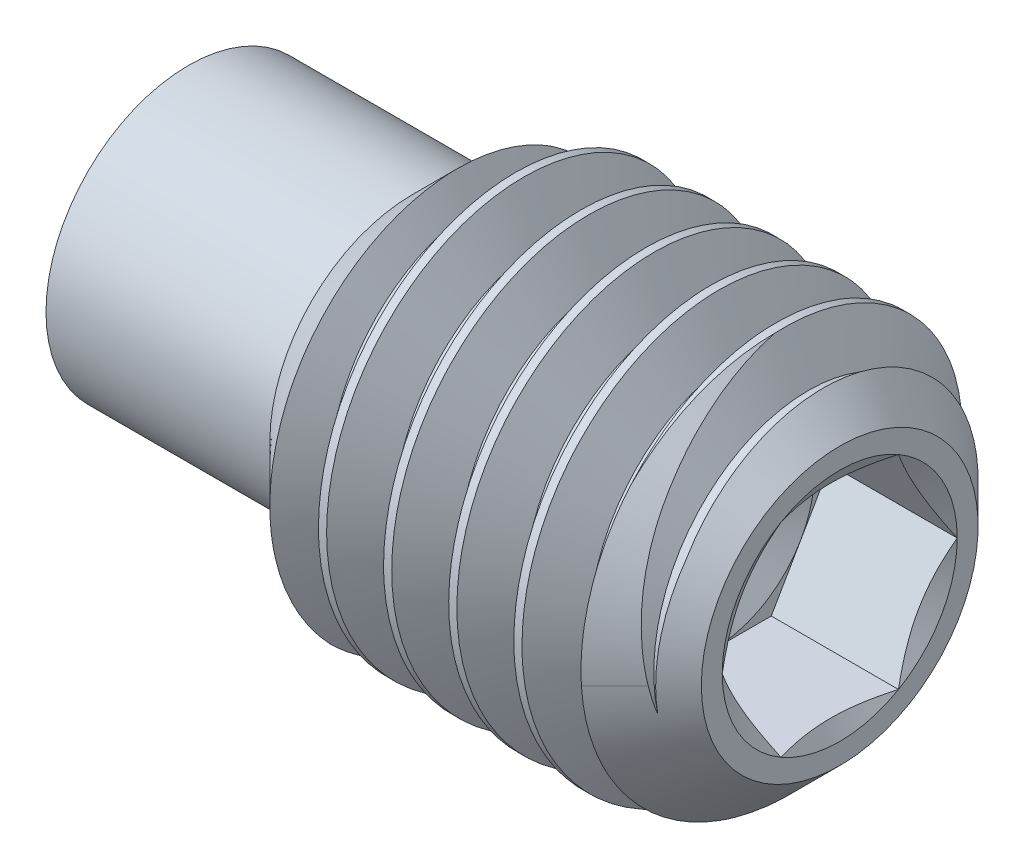
SolidWorks part; units mm, degrees
ref_plane "Front Plane" through (0, 0, 0) normal (0, 0, 1) x (1, 0, 0)
ref_plane "Top Plane" through (0, 0, 0) normal (0, 1, 0) x (1, 0, 0)
ref_plane "Right Plane" through (0, 0, 0) normal (1, 0, 0) x (0, 0, -1)
sketch "Sketch1" plane through (0, 0, 0) normal (0, 0, 1) x (1, 0, 0)
  line L0 (-4, 0) -> (4, 0) construction
  line L1 (4, 2.5) -> (4, -2.5) construction
  line L2 (-4, 1.75) -> (-4, -1.75) construction
  line L3 (4, 2.5) -> (3.2, 2.5) construction
  line L4 (-4, 1.75) -> (-1.25, 1.75) construction
  point P7 (2, -2.5)
  point P10 (4, 1.25)
  dimension "Length | l" = 8
  dimension "Tip Length | z" = 2.75
  dimension "Tip Diameter | dp" = 3.5
  dimension "Thread Diameter | d" = 5
  dimension "Thread Pitch | P1" = 0.8
  dimension "Drive Size | s" = 2.5
  dimension "D1" = 2
sketch "Sketch2" plane through (0, 0, 0) normal (0, 0, 1) x (1, 0, 0)
  line L0 (-4, 0) -> (-4, 1.75)
  line L1 (-4, 1.75) -> (-4, -1.75) construction
  line L2 (-4, 1.75) -> (-1.25, 1.75)
  line L3 (-1.25, 1.75) -> (-0.5, 2.5)
  line L4 (-0.5, 2.5) -> (3.2, 2.5)
  line L5 (4, 2.5) -> (3.2, 2.5) construction
  line L6 (3.2, 2.5) -> (4, 1.7)
  line L7 (4, 2.5) -> (4, -2.5) construction
  line L8 (4, 1.7) -> (4, 0)
  line L9 (4, 0) -> (-4, 0)
  dimension "D1" = 45
  dimension "D2" = 0.8
revolve "Revolve1" add sketch "Sketch2" angle 360 about L0
sketch "Sketch3" plane through (4, 0, 0) normal (1, 0, 0) x (0, 0, -1)
  line L0 (0, 1.75) -> (0, -1.75) construction
  line L1 (0.7217, 1.25) -> (-0.7217, 1.25)
  line L2 (-0.7217, 1.25) -> (-1.4434, 0)
  line L3 (-1.4434, 0) -> (-0.7217, -1.25)
  line L4 (-0.7217, -1.25) -> (0.7217, -1.25)
  line L5 (0.7217, -1.25) -> (1.4434, 0)
  line L6 (1.4434, 0) -> (0.7217, 1.25)
  circle A0 centre (0, 0) radius 1.25 construction
extrude "Cut-Extrude1" cut sketch "Sketch3" against normal blind 1.5625
sketch "Sketch4" plane through (4, 0, 0) normal (1, 0, 0) x (0, 0, -1)
  circle A0 centre (0, 0) radius 1.4434
extrude "Cut-Extrude2" cut sketch "Sketch4" against normal through all draft 60
sketch "Sketch5" plane through (2.4375, 0, 0) normal (1, 0, 0) x (0, 0, -1)
  circle A0 centre (0, 0) radius 1.25
  circle A1 centre (0, 0) radius 1.25 construction
extrude "Cut-Extrude3" cut sketch "Sketch5" against normal through all draft 60
ref_axis "Center Axis 1" through (-4, 0, 0) along (1, 0, 0)
sketch "Sketch6" plane through (0, 0, 0) normal (0, 0, 1) x (1, 0, 0)
  line L0 (4, 2.5) -> (4.35, 1.8938) construction
  line L1 (4.35, 1.8938) -> (4.7, 2.5) construction
  line L2 (4.7, 2.5) -> (4, 2.5) construction
  line L3 (4, 2.5) -> (3.95, 2.5866) construction
  line L4 (3.95, 2.5866) -> (4.75, 2.5866) construction
  line L5 (4.75, 2.5866) -> (4.7, 2.5) construction
  line L6 (4.3, 1.9804) -> (4.4, 1.9804) construction
  line L7 (4.35, 2.5866) -> (4.35, 2.5) construction
  line L8 (4.35, 1.9804) -> (4.35, 1.8938) construction
  line L9 (4, 2.5) -> (3.2, 2.5) construction
  line L10 (3.975, 2.5433) -> (4.725, 2.5433)
  line L11 (4.725, 2.5433) -> (4.4, 1.9804)
  line L12 (4.4, 1.9804) -> (4.3, 1.9804)
  line L13 (4.3, 1.9804) -> (3.975, 2.5433)
  dimension "D1" = 0.1
sketch "Sketch7" plane through (4, 0, 0) normal (1, 0, 0) x (0, 0, -1)
  line L0 (0, 1.75) -> (0, -1.75) construction
  circle A0 centre (0, 0) radius 2.5
curve "Helix/Spiral1" pitch 0.8 height 6.05 radius 2.5 centre (4, 0, 0) axis (-1, 0, 0) start towards (0, 1, 0)
sweep "Cut-Sweep1" cut profiles "Sketch6" path "Helix/Spiral1"
equation "\"D1@Sketch1\"=\"Thread Pitch | P1@Sketch1\" * 2.5"
equation "\"D2@Sketch2\"=\"D1@Sketch1\"*.4"
equation "\"D1@Cut-Extrude1\" = \"Drive Size | s@Sketch1\" * .625"
equation "\"D1@Sketch6\" = \"Thread Pitch | P1@Sketch1\" / 8"
equation "\"D3@Helix/Spiral1\" = \"Length | l@Sketch1\" - \"Tip Length | z@Sketch1\" + \"Thread Pitch | P1@Sketch1\""
equation "\"D4@Helix/Spiral1\"=\"Thread Pitch | P1@Sketch1\""
